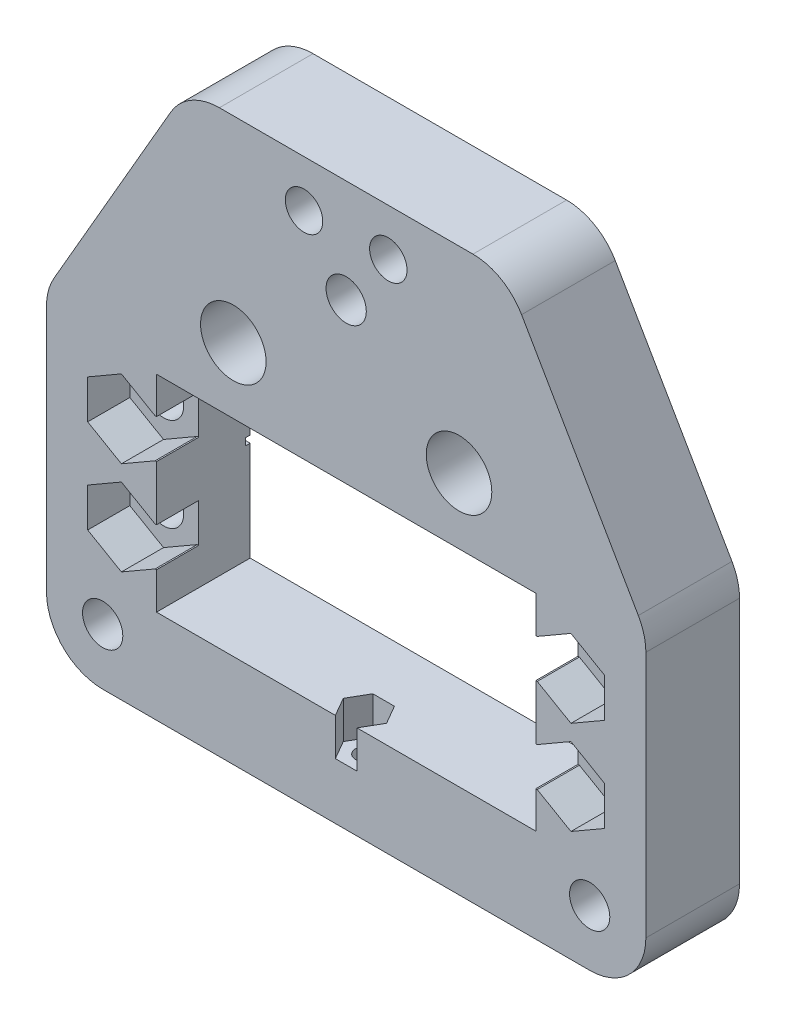
SolidWorks part; units mm, degrees
material "ABS"
ref_plane "Спереди" through (0, 0, 0) normal (0, 0, 1) x (1, 0, 0)
ref_plane "Сверху" through (0, 0, 0) normal (0, 1, 0) x (1, 0, 0)
ref_plane "Справа" through (0, 0, 0) normal (1, 0, 0) x (0, 0, -1)
sketch "Эскиз1" plane through (0, 0, 0) normal (0, 0, 1) x (1, 0, 0)
  line L0 (0, 0) -> (64, 0)
  line L1 (64, 0) -> (64, 34.0192)
  line L2 (64, 34.0192) -> (49, 60)
  line L3 (49, 60) -> (15, 60)
  line L4 (15, 60) -> (0, 34.02)
  line L5 (0, 34.02) -> (0, 0)
  dimension "D1" = 64
  dimension "D2" = 60
  dimension "D3" = 34
  dimension "D4" = 30
  dimension "D5" = 120
  dimension "D6" = 34.02
extrude "Бобышка-Вытянуть1" add sketch "Эскиз1" along normal blind 10 contours L0 L1 L2 L3 L4 L5
fillet "Скругление1" radius 6 6 edges at (49, 60, 5) (15, 60, 5) (0, 34.02, 5) (0, 0, 5) (64, 34.0192, 5) (64, 0, 5)
sketch "Эскиз2" plane through (0, 0, 10) normal (0, 0, 1) x (1, 0, 0)
  line L0 (11.75, 32) -> (52.25, 32)
  line L1 (52.25, 32) -> (52.25, 10)
  line L2 (52.25, 10) -> (11.75, 10)
  line L3 (11.75, 10) -> (11.75, 32)
  line L4 (64, 6) -> (64, 32.4115) construction
  line L5 (6, 0) -> (58, 0) construction
  dimension "D1" = 22
  dimension "D2" = 40.5
  dimension "D3" = 11.75
  dimension "D4" = 10
extrude "Вырез-Вытянуть1" cut sketch "Эскиз2" against normal through all
hole_wizard "Отверстия под штифты Ø4.0 мм1" positions "Эскиз3" profile "Эскиз4" hole size "Ø4.0" standard "Ansi Metric"
sketch "Эскиз3" plane through (0, 0, 10) normal (0, 0, 1) x (1, 0, 0)
  line L0 (45.5359, 60) -> (18.4641, 60) construction
  line L1 (64, 6) -> (64, 32.4115) construction
  line L2 (32, 62.7032) -> (32, 49.5714) construction
  point P0 (27.4999, 55)
  point P2 (36.5, 55)
  point P13 (32, 60)
  dimension "D1" = 5
  dimension "D2" = 27.5
sketch "Эскиз4" plane through (27.4999, 55, 10) normal (1, 0, 0) x (0, -1, 0)
  line L0 (0, 0) -> (0, 7.2017)
  line L1 (0, 7.2017) -> (2, 6)
  line L2 (2, 6) -> (2, 0)
  line L5 (2, 0) -> (0, 0)
  line L10 (0, 7.2017) -> (-2, 6) construction
  line L11 (0, -6.35) -> (0, 107.95) construction
  dimension "Диаметр отверстия" = 4
  dimension "Глубина отверстия" = 6
  dimension "Угол заточки сверла" = 118
hole_wizard "Диаметр отверстия Ø7.0 (7)1" positions "Эскиз5" profile "Эскиз6" hole size "Ø7.0" standard "DIN"
sketch "Эскиз5" plane through (0, 0, 10) normal (0, 0, 1) x (1, 0, 0)
  line L0 (45.5359, 60) -> (18.4641, 60) construction
  line L1 (64, 6) -> (64, 32.4115) construction
  line L2 (32, 62.5774) -> (32, 29.5493) construction
  point P0 (19.9499, 39)
  point P2 (44.05, 39)
  point P13 (32, 60)
  dimension "D1" = 21
  dimension "D2" = 19.95
sketch "Эскиз6" plane through (19.9499, 39, 10) normal (1, 0, 0) x (0, -1, 0)
  line L0 (0, 0) -> (0, 8.103)
  line L1 (0, 8.103) -> (3.5, 6)
  line L2 (3.5, 6) -> (3.5, 0)
  line L5 (3.5, 0) -> (0, 0)
  line L10 (0, 8.103) -> (-3.5, 6) construction
  line L11 (0, -6.35) -> (0, 107.95) construction
  dimension "Диаметр отверстия" = 7
  dimension "Глубина отверстия" = 6
  dimension "Угол заточки сверла" = 118
hole_wizard "Сверло под метчик  спиральное M41" positions "Эскиз7" profile "Эскиз8" hole size "M4x0.7" standard "Ansi Metric" end condition through all
sketch "Эскиз7" plane through (0, 0, 10) normal (0, 0, 1) x (1, 0, 0)
  line L0 (52.25, 10) -> (52.25, 32) construction
  line L1 (52.25, 32) -> (11.75, 32) construction
  line L2 (32, 34.3929) -> (32, 8.0575) construction
  point P0 (56, 26)
  point P2 (56, 16)
  point P4 (8, 26)
  point P6 (8, 16)
  point P25 (32, 32)
  dimension "D1" = 3.75
  dimension "D2" = 6
  dimension "D3" = 10
sketch "Эскиз8" plane through (56, 26, 10) normal (1, 0, 0) x (0, -1, 0)
  line L0 (0, 0) -> (0, 10)
  line L1 (0, 10) -> (2.15, 10)
  line L2 (2.15, 10) -> (2.15, 0)
  line L5 (2.15, 0) -> (0, 0)
  line L11 (0, -6.35) -> (0, 14.6481) construction
  dimension "Диаметр сквозного отверстия" = 4.3
  dimension "Глубина сквозного отверстия" = 10
sketch "Эскиз9" plane through (0, 0, 10) normal (0, 0, -1) x (-1, 0, 0)
  line L0 (-56, 30.803) -> (-56, 10.8409) construction
  line L1 (-56, 30.1569) -> (-59.6, 28.0785)
  line L2 (-59.6, 28.0785) -> (-59.6, 23.9215)
  line L3 (-59.6, 23.9215) -> (-56, 21.8431)
  line L4 (-56, 21.8431) -> (-52.4, 23.9215)
  line L5 (-52.4, 23.9215) -> (-52.4, 28.0785)
  line L6 (-52.4, 28.0785) -> (-56, 30.1569)
  line L7 (-56, 20.1569) -> (-59.6, 18.0785)
  line L8 (-59.6, 18.0785) -> (-59.6, 13.9215)
  line L9 (-59.6, 13.9215) -> (-56, 11.8431)
  line L10 (-56, 11.8431) -> (-52.4, 13.9215)
  line L11 (-52.4, 13.9215) -> (-52.4, 18.0785)
  line L12 (-52.4, 18.0785) -> (-56, 20.1569)
  line L13 (-8, 30.1569) -> (-11.6, 28.0785)
  line L14 (-11.6, 28.0785) -> (-11.6, 23.9215)
  line L15 (-11.6, 23.9215) -> (-8, 21.8431)
  line L16 (-8, 21.8431) -> (-4.4, 23.9215)
  line L17 (-4.4, 23.9215) -> (-4.4, 28.0785)
  line L18 (-4.4, 28.0785) -> (-8, 30.1569)
  line L19 (-8, 20.1569) -> (-11.6, 18.0785)
  line L20 (-11.6, 18.0785) -> (-11.6, 13.9215)
  line L21 (-11.6, 13.9215) -> (-8, 11.8431)
  line L22 (-8, 11.8431) -> (-4.4, 13.9215)
  line L23 (-4.4, 13.9215) -> (-4.4, 18.0785)
  line L24 (-4.4, 18.0785) -> (-8, 20.1569)
  line L25 (-8, 30.803) -> (-8, 11.1079) construction
  circle A0 centre (-56, 26) radius 3.6 construction
  circle A1 centre (-56, 16) radius 3.6 construction
  circle A2 centre (-8, 26) radius 3.6 construction
  circle A3 centre (-8, 16) radius 3.6 construction
  dimension "D1" = 7.2
  dimension "D2" = 7.2
  dimension "D3" = 7.2
  dimension "D4" = 7.2
  dimension "D5" = 60
  dimension "D6" = 60
  dimension "D7" = 60
  dimension "D8" = 60
extrude "Вырез-Вытянуть4" cut sketch "Эскиз9" along normal blind 4.5
sketch "Эскиз12" plane through (0, 10, 0) normal (0, 1, 0) x (1, 0, 0)
  line L0 (32, 0.39) -> (32, -4.7781) construction
  line L7 (45.5359, 0) -> (18.4641, 0) construction
  line L9 (34.3094, -8) -> (33.1547, -6)
  line L10 (33.1547, -6) -> (30.8453, -6)
  line L11 (30.8453, -6) -> (29.6906, -8)
  line L12 (29.6906, -8) -> (30.8453, -10)
  line L13 (30.8453, -10) -> (33.1547, -10)
  line L14 (33.1547, -10) -> (34.3094, -8)
  circle A1 centre (32, -8) radius 2 construction
  point P12 (32, 0)
  dimension "D1" = 4
  dimension "D2" = 8
  dimension "D3" = 30
hole_wizard "Сверло под метчик  спиральное M42" positions "Эскиз16" profile "Эскиз17" hole size "M4x0.7" standard "Ansi Metric" end condition through all
sketch "Эскиз16" plane through (0, 0, 10) normal (0, 0, 1) x (1, 0, 0)
  line L0 (45.5359, 60) -> (18.4641, 60) construction
  line L1 (64, 6) -> (64, 32.4115) construction
  line L2 (6, 0) -> (58, 0) construction
  line L3 (32, -2.539) -> (32, 12.8188) construction
  point P0 (32, 49)
  point P2 (6, 6)
  point P4 (58, 6)
  point P19 (32, 0)
  dimension "D1" = 11
  dimension "D2" = 32
  dimension "D3" = 6
  dimension "D4" = 6
sketch "Эскиз17" plane through (32, 49, 10) normal (1, 0, 0) x (0, -1, 0)
  line L0 (0, 0) -> (0, 10)
  line L1 (0, 10) -> (2.15, 10)
  line L2 (2.15, 10) -> (2.15, 0)
  line L5 (2.15, 0) -> (0, 0)
  line L11 (0, -6.35) -> (0, 15.6845) construction
  dimension "Диаметр сквозного отверстия" = 4.3
  dimension "Глубина сквозного отверстия" = 10
sketch "Эскиз18" plane through (0, 0, 0) normal (0, 0, -1) x (-1, 0, 0)
  line L0 (-32, 53.874) -> (-32, 44.3135) construction
  line L1 (-32, 53.1569) -> (-35.6, 51.0785)
  line L2 (-35.6, 51.0785) -> (-35.6, 46.9215)
  line L3 (-35.6, 46.9215) -> (-32, 44.8431)
  line L4 (-32, 44.8431) -> (-28.4, 46.9215)
  line L5 (-28.4, 46.9215) -> (-28.4, 51.0785)
  line L6 (-28.4, 51.0785) -> (-32, 53.1569)
  line L7 (-58, 10.1569) -> (-61.6, 8.0785)
  line L8 (-61.6, 8.0785) -> (-61.6, 3.9215)
  line L9 (-61.6, 3.9215) -> (-58, 1.8431)
  line L10 (-58, 1.8431) -> (-54.4, 3.9215)
  line L11 (-54.4, 3.9215) -> (-54.4, 8.0785)
  line L12 (-54.4, 8.0785) -> (-58, 10.1569)
  line L13 (-6, 10.1569) -> (-9.6, 8.0785)
  line L14 (-9.6, 8.0785) -> (-9.6, 3.9215)
  line L15 (-9.6, 3.9215) -> (-6, 1.8431)
  line L16 (-6, 1.8431) -> (-2.4, 3.9215)
  line L17 (-2.4, 3.9215) -> (-2.4, 8.0785)
  line L18 (-2.4, 8.0785) -> (-6, 10.1569)
  line L19 (-58, 11.3834) -> (-58, 0.9026) construction
  line L20 (-6, 11.3834) -> (-6, 0.9026) construction
  circle A0 centre (-32, 49) radius 3.6 construction
  circle A1 centre (-58, 6) radius 3.6 construction
  circle A2 centre (-6, 6) radius 3.6 construction
  dimension "D1" = 7.2
  dimension "D2" = 7.2
  dimension "D3" = 7.2
  dimension "D4" = 60
  dimension "D5" = 60
  dimension "D6" = 60
extrude "Вырез-Вытянуть7" cut sketch "Эскиз18" against normal blind 3.2
sketch "Эскиз19" plane through (52.25, 0, 0) normal (-1, 0, 0) x (0, 0, 1)
  line L0 (10, 28.0785) -> (5.5, 28.0785)
  line L1 (10, 10) -> (10, 32) construction
  line L2 (5.5, 28.0785) -> (5.5, 23.9215)
  line L3 (5.5, 23.9215) -> (10, 23.9215)
  line L4 (10, 23.9215) -> (10, 28.0785)
  dimension "D1" = 4.5
extrude "Вырез-Вытянуть13" cut sketch "Эскиз19" against normal blind 0.15 contours L3 L4 L0 L2
sketch "Эскиз21" plane through (11.75, 0, 0) normal (1, 0, 0) x (0, 0, -1)
  line L0 (-10, 28.0785) -> (-5.5, 28.0785)
  line L1 (-10, 32) -> (-10, 10) construction
  line L2 (-5.5, 28.0785) -> (-5.5, 23.9215)
  line L3 (-5.5, 23.9215) -> (-10, 23.9215)
  line L4 (-10, 23.9215) -> (-10, 28.0785)
  dimension "D1" = 4.5
extrude "Вырез-Вытянуть14" cut sketch "Эскиз21" against normal blind 0.15
sketch "Эскиз22" plane through (52.25, 0, 0) normal (-1, 0, 0) x (0, 0, 1)
  line L0 (10, 18.0785) -> (5.5, 18.0785)
  line L1 (10, 10) -> (10, 23.9215) construction
  line L2 (5.5, 18.0785) -> (5.5, 13.9215)
  line L3 (5.5, 13.9215) -> (10, 13.9215)
  line L4 (10, 13.9215) -> (10, 18.0785)
  dimension "D1" = 4.5
extrude "Вырез-Вытянуть15" cut sketch "Эскиз22" against normal blind 0.15
sketch "Эскиз23" plane through (11.75, 0, 0) normal (1, 0, 0) x (0, 0, -1)
  line L0 (-10, 18.0785) -> (-5.5, 18.0785)
  line L1 (-10, 23.9215) -> (-10, 10) construction
  line L2 (-5.5, 18.0785) -> (-5.5, 13.9215)
  line L3 (-5.5, 13.9215) -> (-10, 13.9215)
  line L4 (-10, 13.9215) -> (-10, 18.0785)
  dimension "D1" = 4.5
extrude "Вырез-Вытянуть16" cut sketch "Эскиз23" against normal blind 0.15
extrude "Вырез-Вытянуть17" cut sketch "Эскиз12" against normal blind 4 contours L12 L13 L14 L9 L10 L11
hole_wizard "Сверло под метчик  спиральное M2.21" positions "Эскиз24" profile "Эскиз25" hole size "M2.2x0.45" standard "Ansi Metric"
sketch "Эскиз24" plane through (0, 0, 0) normal (0, -1, 0) x (-1, 0, 0)
  line L0 (-6, 0) -> (-58, 0) construction
  line L1 (-6, -10) -> (-6, 0) construction
  point P0 (-32, -8)
  dimension "D1" = 8
  dimension "D2" = 26
sketch "Эскиз25" plane through (32, 0, 8) normal (1, 0, 0) x (0, 0, -1)
  line L0 (0, 0) -> (0, 10.6009)
  line L1 (0, 10.6009) -> (1, 10)
  line L2 (1, 10) -> (1, 0)
  line L5 (1, 0) -> (0, 0)
  line L10 (0, 10.6009) -> (-1, 10) construction
  line L11 (0, -4.9654) -> (0, 14.7206) construction
  dimension "Диаметр отверстия" = 2
  dimension "Глубина отверстия" = 10
  dimension "Угол заточки сверла" = 118
sketch "Эскиз26" plane through (0, 0, 0) normal (0, 0, -1) x (-1, 0, 0)
  line L0 (-1008.75, 26) -> (48991.25, 26) construction
  line L1 (-1008.75, 16) -> (48991.25, 16) construction
  line L2 (-995.7251, 21.75) -> (49004.2749, 21.75) construction
  line L3 (-993.8158, 20.25) -> (49006.1842, 20.25) construction
  line L4 (-8, -974) -> (-8, 49026) construction
  line L5 (-5, -971.552) -> (-5, 49028.448) construction
  line L6 (-12, -970.5921) -> (-12, 49029.4079) construction
  line L7 (-1009.25, 21) -> (48990.75, 21) construction
  line L8 (-12, 20.25) -> (-5, 20.25)
  line L9 (-12, 20.25) -> (-12, 21.75)
  line L10 (-12, 21.75) -> (-5, 21.75)
  line L11 (-5, 20.25) -> (-5, 21.75)
  line L12 (-12, 20.25) -> (-5, 21.75) construction
  line L13 (-12, 21.75) -> (-5, 20.25) construction
  line L14 (-6, 0) -> (-58, 0) construction
  point P20 (-8.5, 21)
  dimension "D1" = 4.25
  dimension "D2" = 4.25
  dimension "D3" = 3
  dimension "D4" = 4
  dimension "D5" = 7
  dimension "D6" = 1.5
  dimension "D7" = 21
ref_plane "Плоскость1" through (0, 21, 0) normal (0, 1, 0) x (1, 0, 0)
sketch "Эскиз29" plane through (0, 21, 0) normal (0, 1, 0) x (1, 0, 0)
  line L0 (12.75, -1000) -> (12.75, 49000) construction
  line L1 (5.75, 0) -> (49815.4849, 4357.7871) construction
  line L2 (0, -1005.7303) -> (0, 48994.2697) construction
  line L3 (5.75, -1000) -> (5.75, 49000) construction
  line L4 (12, 0) -> (5, 0) construction
  line L10 (64, -1006.9199) -> (64, 48993.0801) construction
  line L12 (32, -998.6843) -> (32, 49001.3157) construction
  line L17 (51.25, 0) -> (51.25, -0.6124)
  line L18 (51.25, -0.6124) -> (58.25, 0)
  line L19 (58.25, 0) -> (51.25, 0)
  line L20 (5.75, 0) -> (12.75, 0)
  line L21 (12.75, -0.6124) -> (5.75, 0)
  line L22 (12.75, 0) -> (12.75, -0.6124)
  dimension "D1" = 5
  dimension "D3" = 32
  dimension "D4" = 64
sketch "Эскиз30" plane through (0, 0, 0) normal (0, 0, -1) x (-1, 0, 0)
  line L0 (-64, -972.7365) -> (-64, 49027.2635) construction
  line L2 (0, -971.7183) -> (0, 49028.2817) construction
  line L4 (-32, -971.4637) -> (-32, 49028.5363) construction
  line L5 (-11.75, 32) -> (-11.75, 10) construction
  dimension "D1" = 32
  dimension "D2" = 32
  dimension "D3" = 20.25
extrude "Вырез-Вытянуть19" cut sketch "Эскиз29" against normal mid plane 0.75 contours L21 L20 L22
extrude "Вырез-Вытянуть20" cut sketch "Эскиз29<3>" against normal mid plane 0.75 contours L18 L19 L17
sketch "Эскиз29<3>" plane through (0, 21, 0) normal (0, 1, 0) x (1, 0, 0) same geometry as "Эскиз29"
